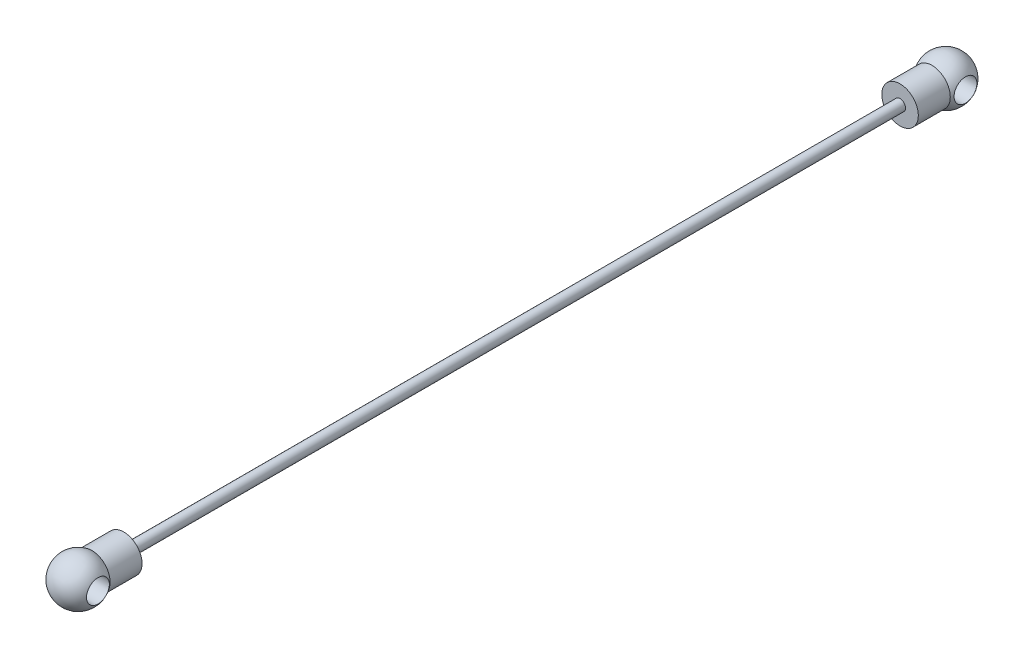
SolidWorks part; units mm, degrees
ref_plane "Front Plane" through (0, 0, 0) normal (0, 0, 1) x (1, 0, 0)
ref_plane "Top Plane" through (0, 0, 0) normal (0, 1, 0) x (1, 0, 0)
ref_plane "Right Plane" through (0, 0, 0) normal (1, 0, 0) x (0, 0, -1)
sketch "Sketch1" plane through (0, 0, 0) normal (0, 0, 1) x (1, 0, 0)
  circle A0 centre (0, 0) radius 0.6
extrude "Boss-Extrude1" add sketch "Sketch1" along normal mid plane 85
sketch "Sketch2" plane through (0, 0, 42.5) normal (0, 0, 1) x (1, 0, 0)
  circle A0 centre (0, 0) radius 2
extrude "Boss-Extrude2" add sketch "Sketch2" along normal blind 5
sketch "Sketch3" plane through (0, 0, 0) normal (0, 1, 0) x (1, 0, 0)
  line L0 (0, -45) -> (0, -50)
  arc A0 (0, -50) -> (0, -45) centre (0, -47.5) ccw
revolve "Revolve1" add sketch "Sketch3" angle 360 about L0
sketch "Sketch6" plane through (0, 0, 0) normal (1, 0, 0) x (0, 0, -1)
  circle A2 centre (-47.5, 0) radius 1.25
extrude "Cut-Extrude2" cut sketch "Sketch6" against normal through all both and the other way through all
mirror "Mirror1" about plane through (0, 0, 0) normal (0, 0, 1) of "Boss-Extrude2", "Revolve1", "Cut-Extrude2"
